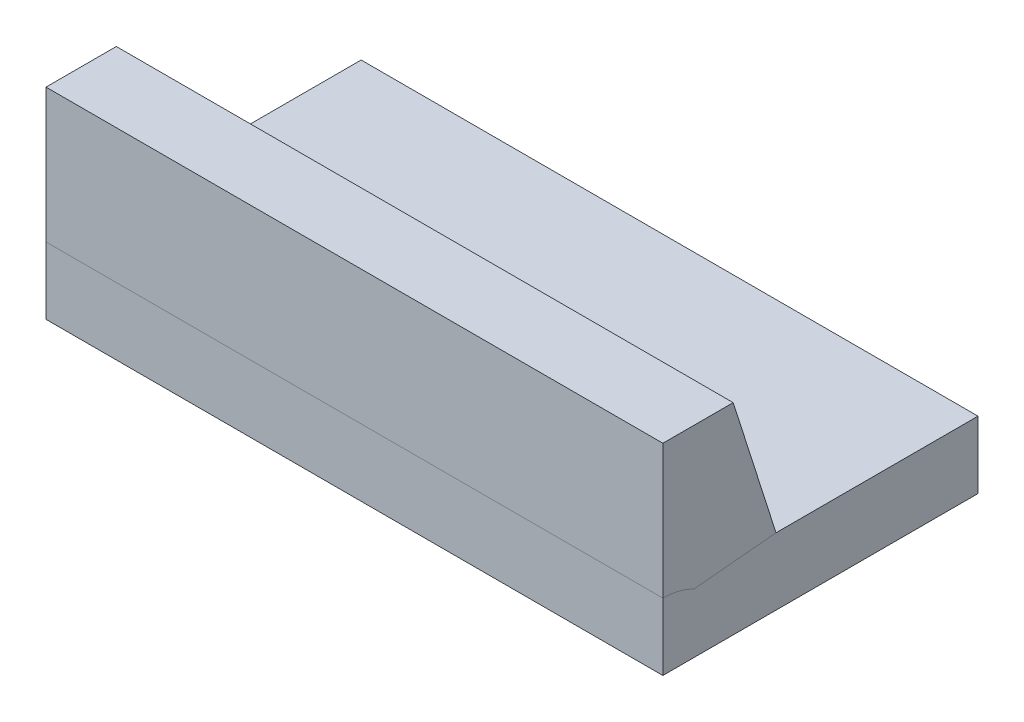
SolidWorks part; units mm, degrees
ref_plane "Front Plane" through (0, 0, 0) normal (0, 0, 1) x (1, 0, 0)
ref_plane "Top Plane" through (0, 0, 0) normal (0, 1, 0) x (1, 0, 0)
ref_plane "Right Plane" through (0, 0, 0) normal (1, 0, 0) x (0, 0, -1)
sketch "Sketch1" plane through (0, 0, 0) normal (0, 1, 0) x (1, 0, 0)
  line L1 (-23.9264, 12.7301) -> (22.0736, 12.7301)
  line L2 (-23.9264, 12.7301) -> (-23.9264, -10.7699)
  line L3 (-23.9264, -10.7699) -> (22.0736, -10.7699)
  line L4 (22.0736, 12.7301) -> (22.0736, -10.7699)
  dimension "D1" = 46
  dimension "D2" = 23.5
extrude "Boss-Extrude1" add sketch "Sketch1" along normal blind 5
sketch "Sketch2" plane through (0, 5, 0) normal (0, 1, 0) x (1, 0, 0)
  line L0 (22.0736, -10.7699) -> (22.0736, 12.7301) construction
  line L1 (22.0736, -0.332) -> (-23.9264, -0.332)
  line L2 (22.0736, -0.332) -> (22.0736, -10.7699)
  line L3 (22.0736, -10.7699) -> (-23.9264, -10.7699)
  line L4 (-23.9264, -0.332) -> (-23.9264, -10.7699)
extrude "Boss-Extrude2" add sketch "Sketch2" along normal blind 10 separate body contours L1 L4 L3 L2
extrude "Boss-Extrude3" add sketch "Sketch1<2>" along normal blind 5
sketch "Sketch1<2>" plane through (0, 0, 0) normal (0, 1, 0) x (1, 0, 0) same geometry as "Sketch1"
sketch "Sketch3" plane through (0, 0, 0) normal (0, -1, 0) x (1, 0, 0)
  circle A0 centre (10.024, -4.312) radius 2
  circle A1 centre (-11.9754, -4.4781) radius 2
extrude "Cut-Extrude1" cut sketch "Sketch3" against normal blind 10
sketch "Sketch4" plane through (22.0736, 0, 0) normal (1, 0, 0) x (0, 0, -1)
  line L0 (-0.332, 5) -> (-2.332, 5)
  line L1 (-2.332, 5) -> (-5.5255, 15)
  line L2 (-0.332, 15) -> (-10.7699, 15) construction
  line L3 (-5.5255, 15) -> (-0.332, 15)
  line L4 (-0.332, 15) -> (-0.332, 5)
  circle A0 centre (-10.7699, 0) radius 5
  dimension "D1" = 2
extrude "Cut-Extrude2" cut sketch "Sketch4" against normal through all both
